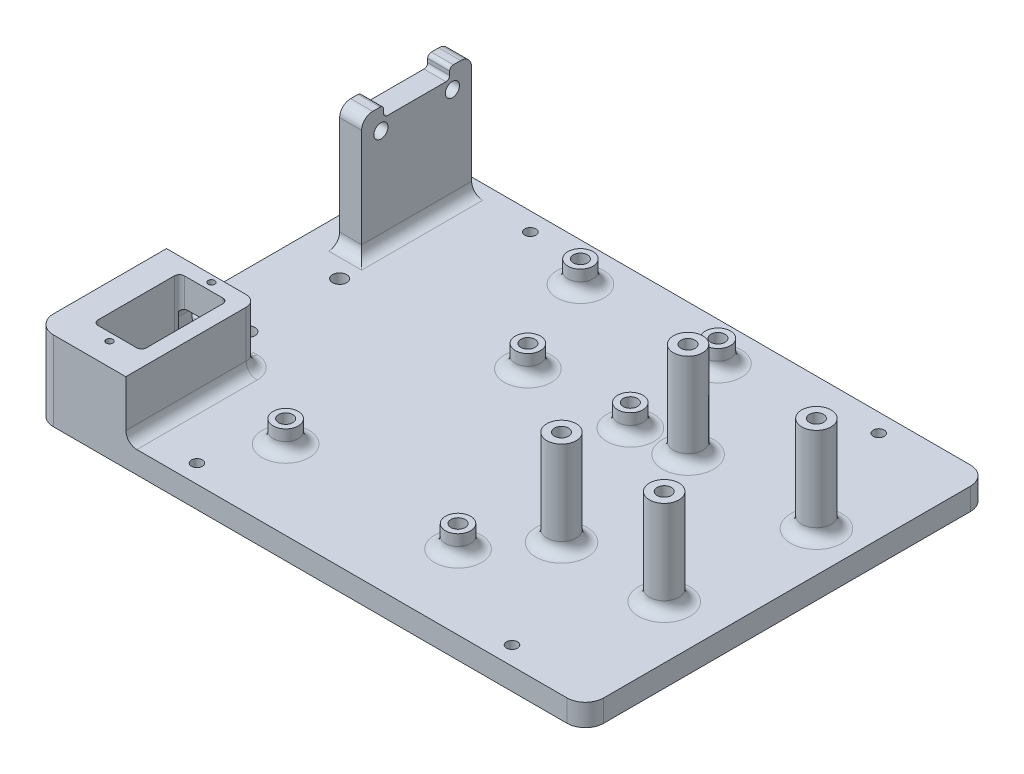
SolidWorks part; units mm, degrees
ref_plane "Front Plane" through (0, 0, 0) normal (0, 0, 1) x (1, 0, 0)
ref_plane "Top Plane" through (0, 0, 0) normal (0, 1, 0) x (1, 0, 0)
ref_plane "Right Plane" through (0, 0, 0) normal (1, 0, 0) x (0, 0, -1)
sketch "Sketch1" plane through (0, 0, 0) normal (0, 1, 0) x (1, 0, 0)
  line L1 (0, 0) -> (150, 0)
  line L2 (0, 0) -> (0, 110)
  line L3 (0, 110) -> (150, 110)
  line L4 (150, 0) -> (150, 110)
  dimension "D1" = 150
  dimension "D2" = 110
extrude "Boss-Extrude1" add sketch "Sketch1" along normal blind 6
hole_wizard "#8 (0.199) Diameter Hole1" positions "Sketch2" profile "Sketch3" hole size "#24" standard "ANSI Inch" end condition up to next
sketch "Sketch2" plane through (0, 6, 0) normal (0, 1, 0) x (1, 0, 0)
  point P0 (89.88, 72.39)
  point P3 (61.94, 72.39)
  point P6 (46.7, 21.59)
  point P9 (94.96, 20.32)
  point P24 (49.16, 99.5)
  point P27 (86.66, 99.5)
  point P30 (15, 68)
  point P33 (15, 43)
sketch "Sketch3" plane through (89.88, 6, -72.39) normal (1, 0, 0) x (0, 0, 1)
  line L0 (0, 0) -> (0, 6)
  line L1 (0, 6) -> (1.9304, 6)
  line L2 (1.9304, 6) -> (1.9304, 0)
  line L5 (1.9304, 0) -> (0, 0)
  line L11 (0, -6.35) -> (0, 107.95) construction
  dimension "Thru Hole Dia." = 3.8608
  dimension "Thru Hole Depth" = 6
sketch "Sketch4" plane through (0, 6, 0) normal (0, 1, 0) x (1, 0, 0)
  line L0 (150, 110) -> (0, 110) construction
  line L1 (7, 106) -> (13, 106)
  line L2 (7, 106) -> (7, 76)
  line L3 (7, 76) -> (13, 76)
  line L4 (13, 106) -> (13, 76)
  line L5 (0, 110) -> (0, 0) construction
  dimension "D1" = 30
  dimension "D2" = 6
  dimension "D3" = 4
  dimension "D4" = 7
extrude "Boss-Extrude2" add sketch "Sketch4" along normal blind 30
ref_plane "Plane1" through (0, 0, -91) normal (0, 0, -1) x (-1, 0, 0)
hole_wizard "#24 (0.152) Diameter Hole1" positions "Sketch5" profile "Sketch6" hole size "#24" standard "ANSI Inch" end condition up to next
sketch "Sketch5" plane through (7, 0, 0) normal (-1, 0, 0) x (0, 0, 1)
  point P0 (-81.25, 33.27)
  point P3 (-100.75, 33.27)
sketch "Sketch6" plane through (7, 33.27, -81.25) normal (0, 1, 0) x (0, 0, 1)
  line L0 (0, 0) -> (0, 6)
  line L1 (0, 6) -> (1.9304, 6)
  line L2 (1.9304, 6) -> (1.9304, 0)
  line L5 (1.9304, 0) -> (0, 0)
  line L11 (0, -6.35) -> (0, 107.95) construction
  dimension "Thru Hole Dia." = 3.8608
  dimension "Thru Hole Depth" = 6
sketch "Sketch7" plane through (0, 36, 0) normal (0, 1, 0) x (1, 0, 0)
  line L0 (13, 76) -> (13, 106) construction
  line L1 (7, 106) -> (13, 106)
  line L2 (7, 106) -> (7, 100)
  line L3 (7, 100) -> (13, 100)
  line L4 (13, 106) -> (13, 100)
  line L6 (7, 76) -> (13, 76)
  line L7 (7, 76) -> (7, 82)
  line L8 (7, 82) -> (13, 82)
  line L9 (13, 76) -> (13, 82)
  dimension "D1" = 6
  dimension "D2" = 6
extrude "Boss-Extrude3" add sketch "Sketch7" along normal blind 3
sketch "Sketch9" plane through (0, 6, 0) normal (0, 1, 0) x (1, 0, 0)
  line L0 (20.2, 9.65) -> (20.2, 30.45) construction
  line L1 (8.85, 8.8) -> (19.35, 8.8) construction
  line L2 (8, 30.45) -> (8, 9.65) construction
  line L3 (19.35, 31.3) -> (8.85, 31.3) construction
  line L4 (20.2, 9.65) -> (20.2, 30.45) construction
  line L5 (8.85, 8.8) -> (19.35, 8.8) construction
  line L6 (8, 30.45) -> (8, 9.65) construction
  line L7 (19.35, 31.3) -> (8.85, 31.3) construction
  line L8 (20.7, 9.65) -> (20.7, 30.45)
  line L9 (19.35, 31.8) -> (8.85, 31.8)
  line L10 (7.5, 30.45) -> (7.5, 9.65)
  line L11 (8.85, 8.3) -> (19.35, 8.3)
  line L13 (0, 0) -> (24.7, 0)
  line L14 (0, 0) -> (0, 35.8)
  line L15 (0, 35.8) -> (24.7, 35.8)
  line L16 (24.7, 0) -> (24.7, 35.8)
  arc A0 (20.2, 30.45) -> (19.35, 31.3) centre (19.35, 30.45) ccw construction
  arc A1 (19.35, 8.8) -> (20.2, 9.65) centre (19.35, 9.65) ccw construction
  arc A2 (8, 9.65) -> (8.85, 8.8) centre (8.85, 9.65) ccw construction
  arc A3 (8.85, 31.3) -> (8, 30.45) centre (8.85, 30.45) ccw construction
  arc A4 (20.2, 30.45) -> (19.35, 31.3) centre (19.35, 30.45) ccw construction
  arc A5 (19.35, 8.8) -> (20.2, 9.65) centre (19.35, 9.65) ccw construction
  arc A6 (8, 9.65) -> (8.85, 8.8) centre (8.85, 9.65) ccw construction
  arc A7 (8.85, 31.3) -> (8, 30.45) centre (8.85, 30.45) ccw construction
  arc A8 (20.7, 30.45) -> (19.35, 31.8) centre (19.35, 30.45) ccw
  arc A9 (8.85, 31.8) -> (7.5, 30.45) centre (8.85, 30.45) ccw
  arc A10 (7.5, 9.65) -> (8.85, 8.3) centre (8.85, 9.65) ccw
  arc A11 (19.35, 8.3) -> (20.7, 9.65) centre (19.35, 9.65) ccw
  dimension "D2" = 4
  dimension "D3" = 4
  dimension "D1" = 0.5
extrude "Boss-Extrude4" add sketch "Sketch9" along normal blind 15.7
sketch "Sketch10" plane through (0, 0, -35.8) normal (0, 0, -1) x (-1, 0, 0)
  line L0 (-7, 39) -> (-7, 6) construction
  line L1 (-20.7, 6) -> (-7, 6)
  line L2 (-20.7, 6) -> (-20.7, 14)
  line L3 (-20.7, 14) -> (-7, 14)
  line L4 (-7, 6) -> (-7, 14)
  dimension "D1" = 8
extrude "Cut-Extrude1" cut sketch "Sketch10" against normal up to surface (4.5 mm away)
sketch "Sketch11" plane through (0, 6, 0) normal (0, 1, 0) x (1, 0, 0)
  arc A0 (108.75, 36) -> (106.25, 36) centre (107.5, 36) ccw construction
  arc A1 (136.75, 36) -> (134.25, 36) centre (135.5, 36) ccw construction
  arc A2 (140.25, 74) -> (137.75, 74) centre (139, 74) ccw construction
  arc A3 (105.25, 74) -> (102.75, 74) centre (104, 74) ccw construction
  arc A4 (108.75, 36) -> (106.25, 36) centre (107.5, 36) ccw construction
  arc A5 (136.75, 36) -> (134.25, 36) centre (135.5, 36) ccw construction
  arc A6 (140.25, 74) -> (137.75, 74) centre (139, 74) ccw construction
  arc A7 (105.25, 74) -> (102.75, 74) centre (104, 74) ccw construction
  circle A8 centre (104, 74) radius 4
  circle A9 centre (139, 74) radius 4
  circle A10 centre (107.5, 36) radius 4
  circle A11 centre (135.5, 36) radius 4
  dimension "D1" = 8
extrude "Boss-Extrude5" add sketch "Sketch11" along normal blind 26
hole_wizard "#24 (0.152) Diameter Hole2" positions "Sketch12" profile "Sketch13" hole size "#24" standard "ANSI Inch" end condition up to next
sketch "Sketch12" plane through (0, 32, 0) normal (0, 1, 0) x (1, 0, 0)
  point P0 (104, 74)
  point P3 (139, 74)
  point P6 (107.5, 36)
  point P9 (135.5, 36)
sketch "Sketch13" plane through (104, 32, -74) normal (1, 0, 0) x (0, 0, 1)
  line L0 (0, 0) -> (0, 32)
  line L1 (0, 32) -> (1.9304, 32)
  line L2 (1.9304, 32) -> (1.9304, 0)
  line L5 (1.9304, 0) -> (0, 0)
  line L11 (0, -6.35) -> (0, 107.95) construction
  dimension "Thru Hole Dia." = 3.8608
  dimension "Thru Hole Depth" = 32
fillet "Fillet3" radius 5 4 edges at (150, 3, -110) (150, 3, 0) (0, 10.85, 0) (0, 3, -110)
sketch "Sketch17" plane through (0, 6, 0) normal (0, 1, 0) x (1, 0, 0)
  circle A0 centre (94.96, 20.32) radius 1.9304 construction
  circle A1 centre (46.7, 21.59) radius 1.9304 construction
  circle A2 centre (89.88, 72.39) radius 1.9304 construction
  circle A3 centre (61.94, 72.39) radius 1.9304 construction
  circle A4 centre (86.66, 99.5) radius 1.9304 construction
  circle A5 centre (49.16, 99.5) radius 1.9304 construction
  circle A6 centre (94.96, 20.32) radius 1.9304
  circle A7 centre (46.7, 21.59) radius 1.9304
  circle A8 centre (89.88, 72.39) radius 1.9304
  circle A9 centre (61.94, 72.39) radius 1.9304
  circle A10 centre (86.66, 99.5) radius 1.9304
  circle A11 centre (49.16, 99.5) radius 1.9304
  circle A12 centre (49.16, 99.5) radius 3.4304
  circle A13 centre (86.66, 99.5) radius 3.4304
  circle A14 centre (61.94, 72.39) radius 3.4304
  circle A15 centre (89.88, 72.39) radius 3.4304
  circle A16 centre (46.7, 21.59) radius 3.4304
  circle A17 centre (94.96, 20.32) radius 3.4304
  dimension "D1" = 1.5
extrude "Boss-Extrude6" add sketch "Sketch17" along normal blind 6
fillet "Fillet4" radius 3 20 edges at (107.5, 6, -40) (10, 39, -76) (10, 39, -106) (10, 6, -76) (13, 6, -91) (20.7, 14, -33.55) (7, 14, -33.55) (24.7, 13.85, -35.8) (22.7, 6, -35.8) (3.5, 6, -35.8) (24.7, 6, -17.9) (104, 6, -78) (139, 6, -78) (135.5, 6, -40) (49.16, 6, -102.9304) (86.66, 6, -102.9304) (61.94, 6, -75.8204) (89.88, 6, -75.8204) (94.96, 6, -23.7504) (46.7, 6, -25.0204)
fillet "Fillet5" radius 1 4 edges at (10, 36, -100) (10, 39, -100) (10, 39, -82) (10, 36, -82)
hole_wizard "Ø3.0mm Dowel Hole1" positions "Sketch14" profile "Sketch15" hole size "Ø3.0" standard "ANSI Metric" end condition up to next
sketch "Sketch14" plane through (0, 6, 0) normal (0, 1, 0) x (1, 0, 0)
  line L0 (145, 110) -> (5, 110) construction
  line L1 (150, 5) -> (150, 105) construction
  line L3 (27.7, 0) -> (145, 0) construction
  line L4 (0, 105) -> (0, 38.8) construction
  line L6 (34.1, 0) -> (34.1, 40.2) construction
  point P0 (30, 105)
  point P2 (39.1, 5)
  point P4 (125, 5)
  point P6 (125, 105)
  dimension "D1" = 5
  dimension "D2" = 25
  dimension "D3" = 5
  dimension "D4" = 5
  dimension "D5" = 30
sketch "Sketch15" plane through (30, 6, -105) normal (1, 0, 0) x (0, 0, 1)
  line L0 (0, 0) -> (0, 6)
  line L1 (0, 6) -> (1.5, 6)
  line L2 (1.5, 6) -> (1.5, 0)
  line L5 (1.5, 0) -> (0, 0)
  line L11 (0, -6.35) -> (0, 107.95) construction
  dimension "Thru Hole Dia." = 3
  dimension "Thru Hole Depth" = 6
sketch "Sketch16" plane through (0, 21.7, 0) normal (0, 1, 0) x (1, 0, 0)
  circle A0 centre (14.1, 6.15) radius 0.9
  circle A1 centre (14.1, 33.95) radius 0.9
  dimension "D1" = 1.8
  dimension "D2" = 1.8
extrude "Cut-Extrude2" cut sketch "Sketch16" against normal blind 5
